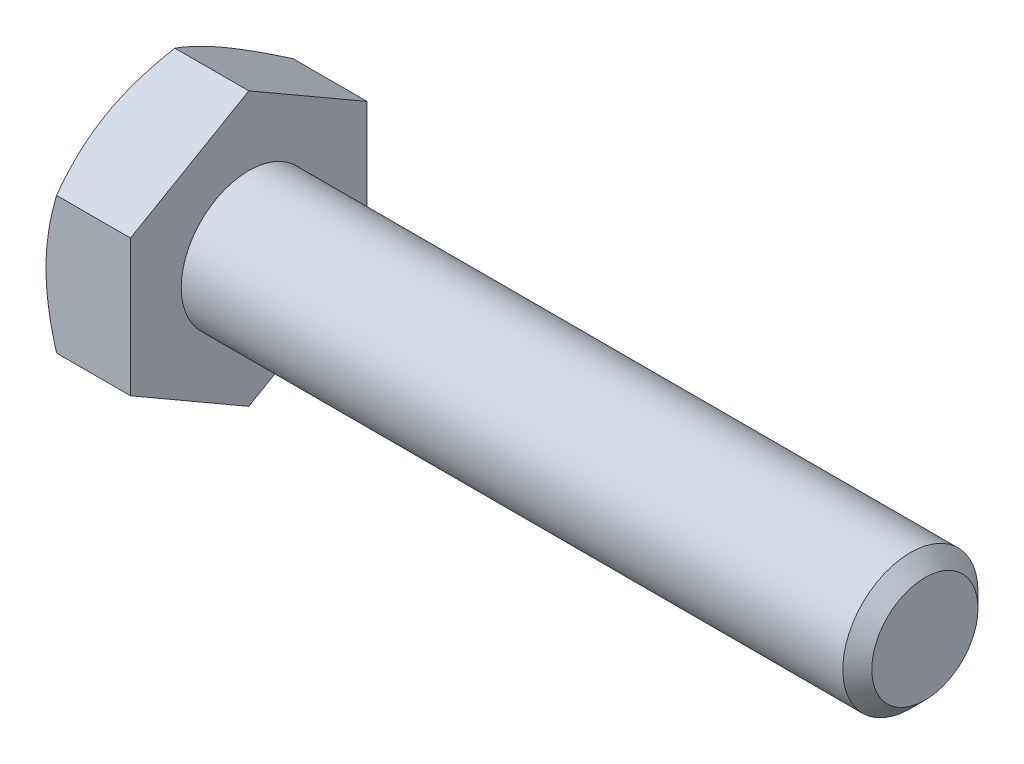
SolidWorks part; units mm, degrees
material "Alloy Steel (SS)"
ref_plane "Front Plane" through (0, 0, 0) normal (0, 0, 1) x (1, 0, 0)
ref_plane "Top Plane" through (0, 0, 0) normal (0, 1, 0) x (1, 0, 0)
ref_plane "Right Plane" through (0, 0, 0) normal (1, 0, 0) x (0, 0, -1)
sketch "Sketch1" plane through (0, 0, 0) normal (0, 0, 1) x (1, 0, 0)
  line L0 (-17.8594, 0) -> (17.8594, 0) construction
  line L1 (17.8594, 3.175) -> (17.8594, -3.175) construction
  line L2 (-13.8906, 5.5562) -> (-13.8906, -5.5562) construction
  line L3 (-17.8594, 5.5562) -> (-17.8594, -5.5562) construction
  point P9 (-13.8906, 0)
  point P10 (14.6844, -3.175)
  dimension "Screw Dia" = 6.35
  dimension "Hex" = 11.1125
  dimension "Head Ht" = 3.9688
  dimension "Screw Lenght" = 31.75
  dimension "D1" = 3.175
ref_plane "Plane2" through (17.8594, 0, 0) normal (1, 0, 0) x (0, 0, -1)
sketch "Sketch5" plane through (17.8594, 0, 0) normal (1, 0, 0) x (0, 0, -1)
  circle A0 centre (0, 0) radius 3.175
extrude "Boss-Extrude3" add sketch "Sketch5" against normal up to vertex (31.75 mm away) up to point (-13.8906, 0, 0)
sketch "Sketch9" plane through (17.8594, 0, 0) normal (1, 0, 0) x (0, 0, -1)
  circle A1 centre (0, 0) radius 3.175
  circle A2 centre (0, 0) radius 3.175
  dimension "D1" = 0
curve "Helix/Spiral1" pitch 0.9071 height 19.9571 turns 22 parameters "Pitch"=0.9071
chamfer "Chamfer1" distance 0.6804 angle 45 1 edges at (17.8594, 0, -3.175)
sketch "Sketch10" plane through (0, 0, 0) normal (0, 0, 1) x (1, 0, 0)
  line L0 (17.8594, 3.175) -> (18.1996, 2.5858)
  line L1 (18.1996, 2.5858) -> (18.3129, 2.5858)
  line L2 (18.3129, 2.5858) -> (18.6531, 3.175)
  line L3 (17.8594, 3.175) -> (18.6531, 3.175)
  line L4 (18.2562, 3.175) -> (18.2562, 2.5858) construction
  line L5 (18.0295, 2.8804) -> (18.483, 2.8804) construction
  dimension "D1" = 60
  dimension "D2" = 0.1134
  dimension "D3" = 0.4536
sweep "Cut-Sweep1" [suppressed] cut profiles "Sketch10" path "Helix/Spiral1"
sketch "Sketch11" plane through (0, 0, 0) normal (0, 0, 1) x (1, 0, 0)
  line L0 (-13.8906, 3.175) -> (-13.8906, 0)
  line L1 (-13.8906, 0) -> (1.9844, 0)
  line L3 (1.9844, 0) -> (-1.1906, 3.175)
  line L4 (-13.8906, 3.175) -> (-1.1906, 3.175)
  dimension "D1" = 45
  dimension "MIn Thread" = 19.05
revolve "Revolve1" [suppressed] add sketch "Sketch11" angle 360 about L1
sketch "Sketch6" plane through (-13.8906, 0, 0) normal (-1, 0, 0) x (0, 0, 1)
  line L0 (0, 5.5562) -> (0, -5.5562) construction
  line L1 (5.5563, 3.2079) -> (0, 6.4158)
  line L2 (0, 6.4158) -> (-5.5562, 3.2079)
  line L3 (-5.5562, 3.2079) -> (-5.5562, -3.2079)
  line L4 (-5.5562, -3.2079) -> (0, -6.4158)
  line L5 (0, -6.4158) -> (5.5563, -3.2079)
  line L6 (5.5563, -3.2079) -> (5.5563, 3.2079)
  circle A0 centre (0, 0) radius 5.5563 construction
extrude "Boss-Extrude4" add sketch "Sketch6" along normal up to vertex (3.9688 mm away) up to point (-17.8594, -5.5562, 0)
sketch "Sketch7" plane through (-17.8594, 0, 0) normal (-1, 0, 0) x (0, 0, 1)
  circle A0 centre (0, 0) radius 5.5563 construction
  circle A1 centre (0, 0) radius 5.5563
sketch "Sketch8" plane through (-17.8594, 0, 0) normal (-1, 0, 0) x (0, 0, 1)
  circle A0 centre (0, 0) radius 5.5563 construction
  circle A1 centre (0, 0) radius 5.5563
extrude "Cut-Extrude3" cut sketch "Sketch8" against normal through all draft 60 flip side to cut
sketch "Sketch12" plane through (-17.8594, 0, 0) normal (-1, 0, 0) x (0, 0, 1)
  line L0 (0, 4.2783) -> (0, 2.3892) construction
  line L1 (0.1667, 4.2783) -> (0.1667, 2.3892)
  line L2 (-0.1667, 4.2783) -> (-0.1667, 2.3892)
  line L3 (0, 3.175) -> (0, -3.175) construction
  arc A0 (0.1667, 4.2783) -> (-0.1667, 4.2783) centre (0, 4.2783) ccw
  arc A1 (-0.1667, 2.3892) -> (0.1667, 2.3892) centre (0, 2.3892) ccw
  circle A3 centre (0, 0) radius 2.2225 construction
  circle A4 centre (0, 0) radius 4.445 construction
  point P2 (0, 3.3337)
  dimension "D1" = 4.445
  dimension "D3" = 8.89
  dimension "D2" = 0.3334
extrude "Cut-Extrude4" cut sketch "Sketch12" against normal blind 0.254
pattern_circular "CirPattern1" count 3 over 360 about axis through (-13.8906, 0, 0) along (1, 0, 0) of "Cut-Extrude4"
equation "\"D2@Sketch10\" = \"Pitch@Helix/Spiral1\"*.125"
equation "\"D3@Sketch10\" = \"Pitch@Helix/Spiral1\"*.5"
equation "\"D3@Helix/Spiral1\" = \"MIn Thread@Sketch11\"+\"Pitch@Helix/Spiral1\""
equation "\"D1@Chamfer1\" = \"Pitch@Helix/Spiral1\"*.75"
equation "\"D1@Sketch12\" = \"Hex@Sketch1\"*.4"
equation "\"D3@Sketch12\" = \"Hex@Sketch1\"*.8"
equation "\"D2@Sketch12\" = \"Hex@Sketch1\"*.03"
equation "\"D1@Sketch1\" = \"Pitch@Helix/Spiral1\"*3.5"
